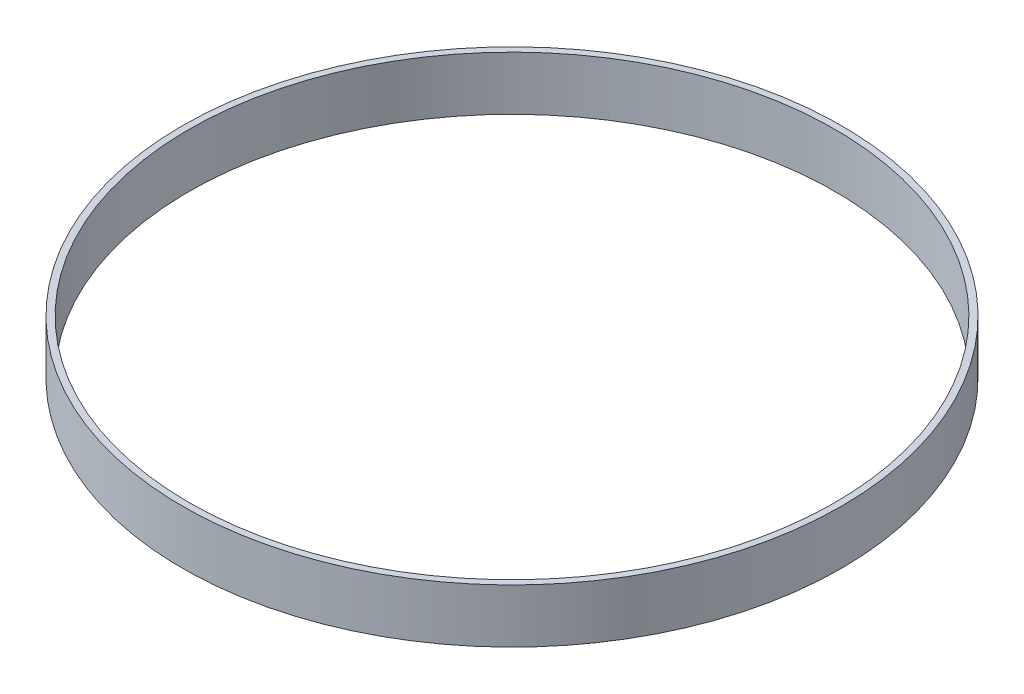
SolidWorks part; units mm, degrees
ref_plane "Front Plane" through (0, 0, 0) normal (0, 0, 1) x (1, 0, 0)
ref_plane "Top Plane" through (0, 0, 0) normal (0, 1, 0) x (1, 0, 0)
ref_plane "Right Plane" through (0, 0, 0) normal (1, 0, 0) x (0, 0, -1)
sketch "Sketch1" plane through (0, 0, 0) normal (0, 1, 0) x (1, 0, 0)
  circle A0 centre (0, 0) radius 60
  dimension "D1" = 120
extrude "Extrude-Thin1" add sketch "Sketch1" along normal blind 10 thin contours A0 thin type one direction wall 1.2
